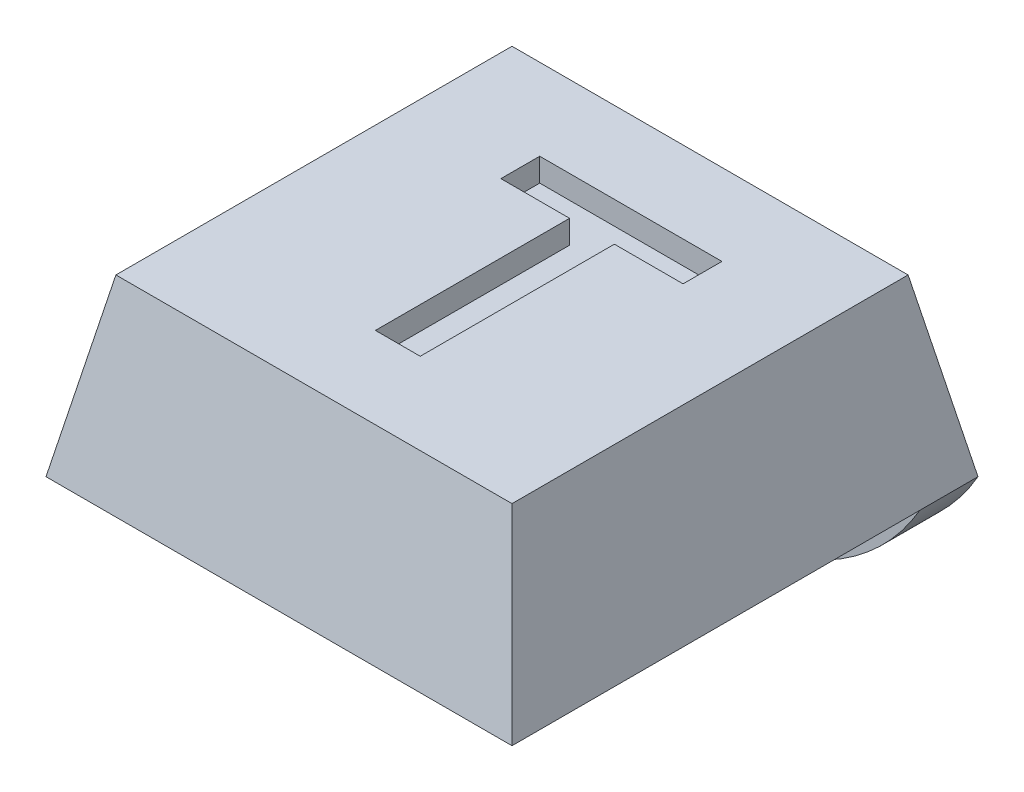
SolidWorks part; units mm, degrees
ref_plane "Front Plane" through (0, 0, 0) normal (0, 0, 1) x (1, 0, 0)
ref_plane "Top Plane" through (0, 0, 0) normal (0, 1, 0) x (1, 0, 0)
ref_plane "Right Plane" through (0, 0, 0) normal (1, 0, 0) x (0, 0, -1)
sketch "Sketch1" plane through (0, 0, 0) normal (0, 1, 0) x (1, 0, 0)
  line L1 (0, 0) -> (8, 0)
  line L2 (0, 0) -> (0, 8)
  line L3 (0, 8) -> (8, 8)
  line L4 (8, 0) -> (8, 8)
  dimension "D1" = 8
  dimension "D2" = 8
extrude "Boss-Extrude1" add sketch "Sketch1" along normal blind 3
sketch "Sketch2" plane through (0, 0, 0) normal (0, 0, 1) x (1, 0, 0)
  line L0 (0, 0) -> (0.6, 3)
  line L1 (0, 3) -> (8, 3) construction
  line L2 (0.6, 3) -> (0, 3)
  line L3 (0, 3) -> (0, 0)
  line L4 (8, 0) -> (7.4, 3)
  line L5 (7.4, 3) -> (8, 3)
  line L6 (8, 3) -> (8, 0)
  dimension "D1" = 0.6
  dimension "D2" = 0.6
extrude "Cut-Extrude1" cut sketch "Sketch2" against normal through all both and the other way through all
sketch "Sketch3" plane through (0, 0, 0) normal (1, 0, 0) x (0, 0, -1)
  line L0 (0, 0) -> (0.6, 3)
  line L1 (8, 3) -> (0, 3) construction
  line L2 (0.6, 3) -> (0, 3)
  line L3 (0, 3) -> (0, 0)
  line L4 (8, 3) -> (7.4, 3)
  line L5 (7.4, 3) -> (8, 0)
  line L6 (8, 3) -> (8, 0)
  dimension "D1" = 0.6
  dimension "D2" = 0.6
extrude "Cut-Extrude2" cut sketch "Sketch3" along normal blind 11
sketch "Sketch4" plane through (0, 0, 0) normal (0, -1, 0) x (1, 0, 0)
  line L0 (8, 0) -> (8, -8) construction
  line L3 (0, 0) -> (8, 0) construction
  circle A0 centre (4, -3.75) radius 1.8
  dimension "D1" = 3.6
  dimension "D2" = 4
  dimension "D3" = 3.75
extrude "Cut-Extrude3" cut sketch "Sketch4" against normal blind 0.8
sketch "Sketch5" plane through (0, 0, 0) normal (0, -1, 0) x (1, 0, 0)
  line L0 (8, 0) -> (8, -8) construction
  line L1 (0, -8) -> (8, -8)
  line L2 (0, -8) -> (0, -7)
  line L3 (0, -7) -> (8, -7)
  line L4 (8, -8) -> (8, -7)
  dimension "D1" = 1
extrude "Boss-Extrude2" add sketch "Sketch5" along normal blind 2
fillet "Fillet1" radius 4 2 edges at (8, -2, -7.5) (0, -2, -7.5)
sketch "Sketch6" plane through (0, 3, 0) normal (0, 1, 0) x (1, 0, 0)
  text T0 "T" font "Arial" height 4
extrude "Cut-Extrude4" cut sketch "Sketch6" against normal blind 0.4
